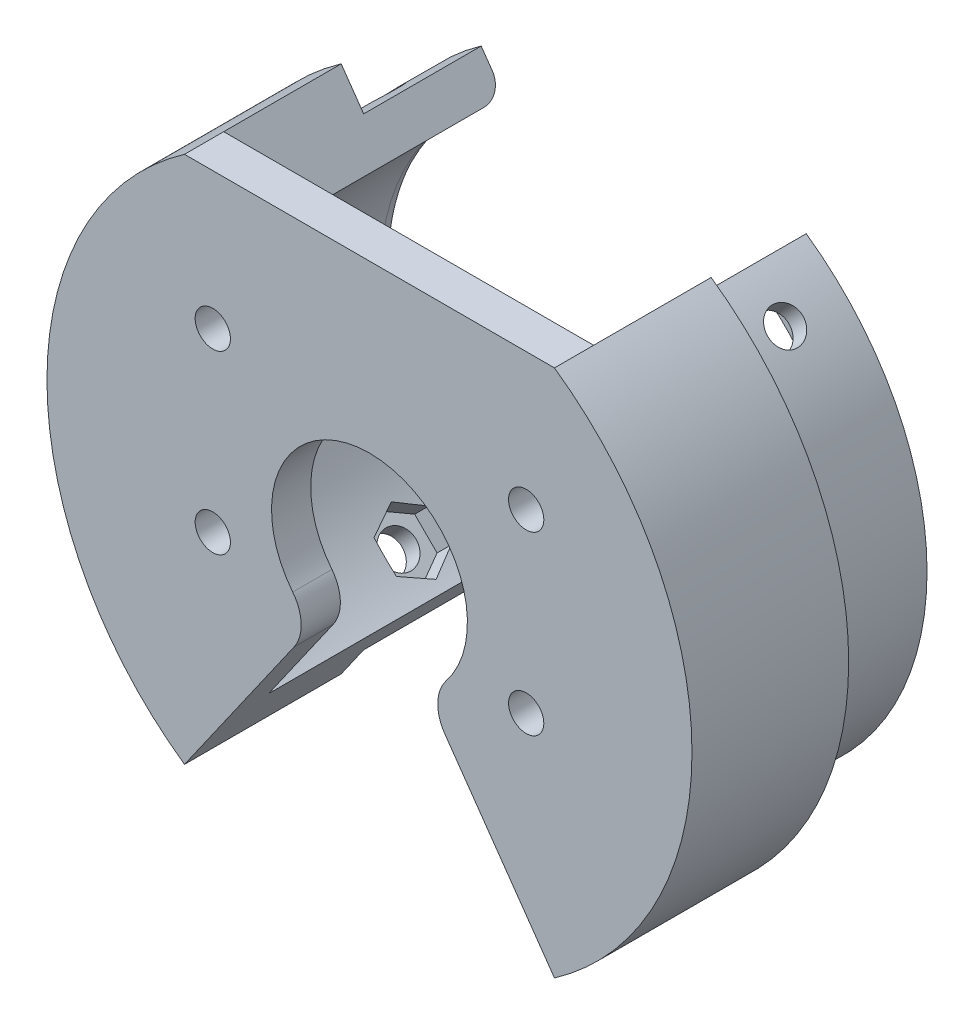
SolidWorks part; units mm, degrees
ref_plane "Front Plane" through (0, 0, 0) normal (0, 0, 1) x (1, 0, 0)
ref_plane "Top Plane" through (0, 0, 0) normal (0, 1, 0) x (1, 0, 0)
ref_plane "Right Plane" through (0, 0, 0) normal (1, 0, 0) x (0, 0, -1)
sketch "Sketch1" plane through (0, 0, 0) normal (0, 0, 1) x (1, 0, 0)
  line L0 (0, 31.1622) -> (0, 36.1622) construction
  circle A0 centre (0, 0) radius 36.1622
  circle A1 centre (0, 0) radius 31.1622
  dimension "D1" = 72.3245
  dimension "D2" = 5
extrude "Boss-Extrude1" add sketch "Sketch1" along normal mid plane 15
sketch "Sketch2" plane through (0, 0, 0) normal (0, 0, 1) x (1, 0, 0)
  line L0 (0, 0) -> (-20.7418, 29.6224) construction
  line L1 (0, 0) -> (0, 36.1622) construction
  line L2 (0, 0) -> (20.7418, 29.6224) construction
  line L3 (20.7418, 29.6224) -> (17.8739, 25.5266)
  line L4 (-17.8739, 25.5266) -> (-20.7418, 29.6224)
  circle A0 centre (0, 0) radius 36.1622 construction
  arc A1 (-17.8739, 25.5266) -> (17.8739, 25.5266) centre (0, 0) cw
  circle A2 centre (0, 0) radius 31.1622 construction
  arc A3 (-20.7418, 29.6224) -> (20.7418, 29.6224) centre (0, 0) cw
  dimension "D1" = 70
extrude "Cut-Extrude1" cut sketch "Sketch2" against normal through all both and the other way through all
mirror "Mirror1" about plane through (0, 0, 0) normal (0, 1, 0) of "Cut-Extrude1"
sketch "Sketch3" plane through (0, 0, 7.5) normal (0, 0, 1) x (1, 0, 0)
  line L0 (-17.8739, 25.5266) -> (-23.6097, 33.7181)
  line L1 (-17.8739, -25.5266) -> (-23.6097, -33.7181)
  line L2 (-20.7418, 29.6224) -> (-17.8739, 25.5266) construction
  line L3 (-20.7418, -29.6224) -> (-17.8739, -25.5266) construction
  line L4 (0, 0) -> (0, 25.5266) construction
  line L5 (17.8739, -25.5266) -> (23.6097, -33.7181)
  line L6 (17.8739, 25.5266) -> (23.6097, 33.7181)
  arc A0 (-17.8739, 25.5266) -> (-17.8739, -25.5266) centre (0, 0) ccw construction
  arc A1 (-17.8739, 25.5266) -> (-17.8739, -25.5266) centre (0, 0) ccw
  arc A2 (-23.6097, -33.7181) -> (-23.6097, 33.7181) centre (0, 0) cw
  arc A3 (23.6097, -33.7181) -> (23.6097, 33.7181) centre (0, 0) ccw
  arc A4 (17.8739, 25.5266) -> (17.8739, -25.5266) centre (0, 0) cw
  dimension "D1" = 10
extrude "Boss-Extrude2" add sketch "Sketch3" along normal blind 15
sketch "Sketch4" plane through (0, 0, 22.5) normal (0, 0, 1) x (1, 0, 0)
  line L0 (23.6097, 33.7181) -> (-23.6097, 33.7181)
  line L1 (23.6097, -33.7181) -> (-23.6097, -33.7181)
  circle A0 centre (0, 0) radius 41.1622 construction
  arc A1 (23.6097, -33.7181) -> (23.6097, 33.7181) centre (0, 0) ccw construction
  arc A2 (-23.6097, -33.7181) -> (-23.6097, 33.7181) centre (0, 0) cw
  arc A3 (23.6097, 33.7181) -> (23.6097, -33.7181) centre (0, 0) cw
extrude "Boss-Extrude3" add sketch "Sketch4" along normal blind 5
ref_plane "Plane1" through (0, 0, 0) normal (0, 0, -1) x (-1, 0, 0)
sketch "Sketch7" plane through (0, 0, 0) normal (0, 0, -1) x (-1, 0, 0)
  line L0 (0, 0) -> (-41.1622, 0) construction
  line L2 (0, 0) -> (-22.035, 22.035) construction
  arc A0 (-23.6097, 33.7181) -> (-23.6097, -33.7181) centre (0, 0) ccw construction
  arc A1 (-17.8739, 25.5266) -> (-17.8739, -25.5266) centre (0, 0) ccw construction
  dimension "D1" = 45
ref_plane "Plane3" through (22.035, 22.035, 0) normal (0.7071, 0.7071, 0) x (0.7071, -0.7071, 0)
sketch "Sketch8" plane through (22.035, 22.035, 0) normal (0.7071, 0.7071, 0) x (0.7071, -0.7071, 0)
  circle A0 centre (0, 0) radius 2.25
  dimension "D1" = 4.5
extrude "Cut-Extrude2" cut sketch "Sketch8" along normal through all and the other way blind 10
sketch "Sketch9" plane through (22.035, 22.035, 0) normal (0.7071, 0.7071, 0) x (0.7071, -0.7071, 0)
  line L1 (2.0207, -3.5) -> (4.0415, 0)
  line L2 (4.0415, 0) -> (2.0207, 3.5)
  line L3 (2.0207, 3.5) -> (-2.0207, 3.5)
  line L4 (-2.0207, 3.5) -> (-4.0415, 0)
  line L5 (-4.0415, 0) -> (-2.0207, -3.5)
  line L6 (-2.0207, -3.5) -> (2.0207, -3.5)
  circle A0 centre (0, 0) radius 3.5 construction
  dimension "D1" = 7
extrude "Cut-Extrude3" cut sketch "Sketch9" along normal blind 2.5 and the other way blind 10
mirror "Mirror2" about plane through (0, 0, 0) normal (0, 1, 0) of "Cut-Extrude3", "Cut-Extrude2"
mirror "Mirror3" about plane through (0, 0, 0) normal (1, 0, 0) of "Mirror2"
sketch "Sketch10" plane through (0, 0, 27.5) normal (0, 0, 1) x (1, 0, 0)
  line L0 (-23.6097, -33.7181) -> (-7.1697, -10.2394)
  line L1 (-23.6097, -33.7181) -> (-17.8739, -25.5266) construction
  line L2 (0, 0) -> (0, -33.7181) construction
  line L3 (-23.6097, -33.7181) -> (23.6097, -33.7181) construction
  line L4 (23.6097, -33.7181) -> (7.1697, -10.2394)
  line L5 (-23.6097, -33.7181) -> (23.6097, -33.7181)
  circle A0 centre (0, 0) radius 12.5 construction
  arc A1 (-7.1697, -10.2394) -> (7.1697, -10.2394) centre (0, 0) cw
  dimension "D1" = 25
extrude "Cut-Extrude4" cut sketch "Sketch10" against normal through all both and the other way through all
fillet "Fillet1" radius 5 2 edges at (7.1697, -10.2394, 25) (-7.1697, -10.2394, 25)
fillet "Fillet2" radius 2.5 2 edges at (31.1622, 0, -7.5) (-31.1622, 0, -7.5)
sketch "Sketch11" plane through (0, 0, 27.5) normal (0, 0, 1) x (1, 0, 0)
  line L1 (-20, -6.25) -> (20, -6.25) construction
  line L2 (-20, -6.25) -> (-20, 16.25) construction
  line L3 (-20, 16.25) -> (20, 16.25) construction
  line L4 (20, -6.25) -> (20, 16.25) construction
  line L5 (0, 16.25) -> (0, -6.25) construction
  line L6 (-20, 5) -> (20, 5) construction
  circle A0 centre (-20, -6.25) radius 2.25
  circle A1 centre (-20, 16.25) radius 2.25
  circle A2 centre (20, 16.25) radius 2.25
  circle A3 centre (20, -6.25) radius 2.25
  point P0 (0, 0)
  point P8 (0, 0)
  point P9 (0, 0)
  point P10 (0, 0)
  point P11 (0, 0)
  point P12 (-3.6571, 0)
  point P13 (0, 0)
  point P14 (-20.7748, -12.6245)
  point P15 (18.7124, -12.7092)
  point P16 (0, 16.6974)
  dimension "D1" = 4.5
  dimension "D2" = 0
  dimension "D3" = 5
  dimension "D4" = 22.5
  dimension "D5" = 40
extrude "example_mount" cut sketch "Sketch11" against normal through all
